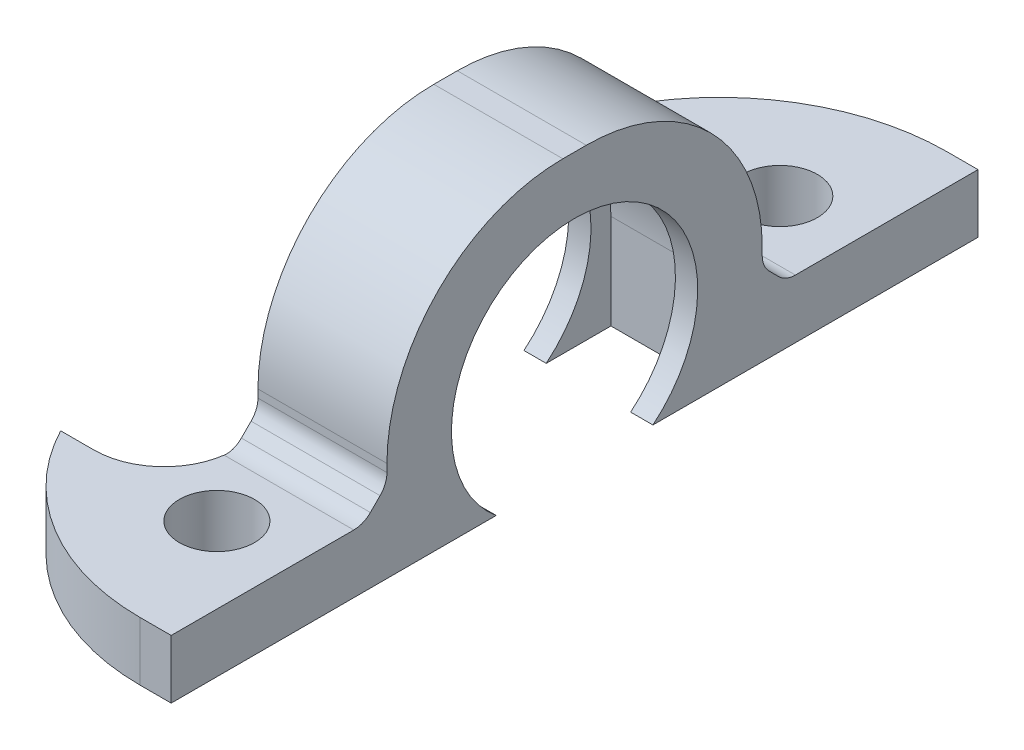
SolidWorks part; units mm, degrees
ref_plane "Front Plane" through (0, 0, 0) normal (0, 0, 1) x (1, 0, 0)
ref_plane "Top Plane" through (0, 0, 0) normal (0, 1, 0) x (1, 0, 0)
ref_plane "Right Plane" through (0, 0, 0) normal (1, 0, 0) x (0, 0, -1)
sketch "Sketch1" plane through (0, 0, 0) normal (0, 1, 0) x (1, 0, 0)
  line L1 (-7.5, -17.5) -> (7.5, -17.5)
  line L2 (-7.5, -17.5) -> (-7.5, 17.5)
  line L3 (-7.5, 17.5) -> (7.5, 17.5)
  line L4 (7.5, -17.5) -> (7.5, 17.5)
  line L5 (-7.5, -17.5) -> (7.5, 17.5) construction
  line L6 (-7.5, 17.5) -> (7.5, -17.5) construction
  point P0 (0, 0)
extrude "Boss-Extrude1" add sketch "Sketch1" along normal blind 2.5
sketch "Sketch2" plane through (0, 0, 0) normal (0, -1, 0) x (-1, 0, 0)
  point P0 (0, 0)
sketch "Sketch3" plane through (0, 0, 0) normal (0, -1, 0) x (1, 0, 0)
  line L0 (2.75, 17.5) -> (2.75, -17.5)
  line L1 (-7.5, 17.5) -> (7.5, 17.5) construction
  line L2 (2.75, 3.4004) -> (2.75, 17.5) construction
  line L3 (7.5, -17.5) -> (-7.5, -17.5) construction
  line L4 (2.75, -17.5) -> (2.75, -19.5) construction
  line M2 (7.5, -17.5) -> (7.5, 17.5)
  line M3 (7.5, 17.5) -> (-7.5, 17.5)
  line M5 (-7.5, -17.5) -> (7.5, -17.5)
extrude "Cut-Extrude2" cut sketch "Sketch3" against normal through all and the other way through all contours L0 M3 M5 M2 region at (5.125, 0, 0)
sketch "Sketch5" plane through (0, 2.5, 0) normal (0, 1, 0) x (1, 0, 0)
  line L0 (2.75, 0) -> (1.75, 0)
  line L1 (2.75, -17.5) -> (2.75, 17.5) construction
  line L2 (1.75, 0) -> (-1.75, 0)
  line L3 (-1.75, 0) -> (-2.75, 0)
  line L4 (-2.75, 0) -> (-8, 0)
  line L6 (-5.75, -12) -> (-10.25, -12)
  line L7 (-2.75, -9) -> (-2.75, 9)
  line L8 (-5.75, 12) -> (-10.25, 12)
  line L9 (-13.25, -9) -> (-13.25, 9)
  line L10 (-2.75, -12) -> (-13.25, 12) construction
  line L11 (-2.75, 12) -> (-13.25, -12) construction
  arc A0 (-10.25, -12) -> (-13.25, -9) centre (-10.25, -9) cw
  arc A1 (-5.75, -12) -> (-2.75, -9) centre (-5.75, -9) ccw
  arc A2 (-2.75, 9) -> (-5.75, 12) centre (-5.75, 9) ccw
  arc A3 (-10.25, 12) -> (-13.25, 9) centre (-10.25, 9) ccw
  line M12 (-7.5, 17.5) -> (-7.5, -17.5)
  dimension "D7" = 3
  dimension "D1" = 1
  dimension "D2" = 3.5
  dimension "D3" = 1
  dimension "D4" = 5.25
  dimension "D5" = 24
  dimension "D6" = 10.5
extrude "Cut-Extrude3" cut sketch "Sketch5" against normal through all contours L8 A3 L9 A0 L6 M12 | L7 A2 L8 L4 M12 | L6 A1 L7 L4 M12 region at (-5.1848, 2.5, 5.8131) region at (-5.1848, 2.5, -5.8131) region at (-10.3115, 2.5, 0)
fillet "Fillet1" radius 10 2 edges at (-7.5, 1.25, 17.5) (-7.5, 1.25, -17.5)
sketch "Sketch6" plane through (0, 2.5, 0) normal (0, 1, 0) x (1, 0, 0)
  line L13 (2.75, 17.2) -> (1.4303, 17.2)
  line L14 (2.75, 17.2) -> (1.4303, 17.2)
  line L16 (1.4303, -17.2) -> (2.75, -17.2)
  line L17 (1.4303, -17.2) -> (2.75, -17.2)
  arc A18 (1.4303, 17.2) -> (-7.2321, 11.865) centre (1.4303, 7.5) ccw
  arc A19 (1.4303, 17.2) -> (-7.2321, 11.865) centre (1.4303, 7.5) ccw
  arc A22 (-7.2321, -11.865) -> (1.4303, -17.2) centre (1.4303, -7.5) ccw
  arc A23 (-7.2321, -11.865) -> (1.4303, -17.2) centre (1.4303, -7.5) ccw
  line M11 (-5.75, -12) -> (-7.5, -12)
  arc M12 (-7.5, -12) -> (1.4303, -17.5) centre (1.4303, -7.5) ccw
  line M13 (1.4303, -17.5) -> (2.75, -17.5)
  line M14 (2.75, -17.5) -> (2.75, 17.5)
  line M15 (2.75, 17.5) -> (1.4303, 17.5)
  arc M16 (1.4303, 17.5) -> (-7.5, 12) centre (1.4303, 7.5) ccw
  line M17 (-7.5, 12) -> (-5.75, 12)
  dimension "D1" = 0.3
  dimension "D2" = 0.3
extrude "Cut-Extrude5" cut sketch "Sketch6" against normal through all contours A19 L14 M14 M15 M16 M17 | A23 L17 M11 M12 M13 M14 region at (2.6337, 2.5, 17.35) region at (2.0901, 2.5, -17.3163)
sketch "Sketch7" plane through (0, 2.5, 0) normal (0, 1, 0) x (1, 0, 0)
  line L0 (0, 0) -> (-0.5, 0)
  line L1 (-0.5, 0) -> (-0.5, 12)
  circle A0 centre (-0.5, 12) radius 1.6
  circle A1 centre (-0.5, -12) radius 1.6
  dimension "D1" = 3.2
  dimension "0.5" = 0.5
extrude "Cut-Extrude6" cut sketch "Sketch7" against normal through all contours A0 | A1 region at (0.5994, 2.5, -10.9006) region at (-0.5, 2.5, 12)
sketch "Sketch8" plane through (2.75, 0, 0) normal (1, 0, 0) x (0, 0, -1)
  line L0 (0, 2.5) -> (0, 4.05)
  line L1 (-17.2, 2.5) -> (17.2, 2.5) construction
  line L2 (8, 2.5) -> (-8, 2.5)
  line L3 (-8, 2.5) -> (-8, 4.5)
  line L4 (8, 2.5) -> (8, 4.5)
  line L5 (0.5, 12) -> (-0.5, 12)
  arc A0 (8, 4.5) -> (0.5, 12) centre (0.5, 4.5) ccw
  arc A1 (-8, 4.5) -> (-0.5, 12) centre (-0.5, 4.5) cw
  circle A2 centre (0, 4.05) radius 5.25
  circle A3 centre (0, 4.05) radius 6.05
  point P8 (0, 2.5)
  dimension "D2" = 7.5
  dimension "D1" = 16
sketch "Sketch9" plane through (2.75, 0, 0) normal (1, 0, 0) x (0, 0, -1)
  line L0 (0, 2.5) -> (-8, 2.5)
  line L1 (-8, 2.5) -> (-8, 4.25)
  line L2 (0, 2.5) -> (8, 2.5)
  line L3 (8, 2.5) -> (8, 4.25)
  line L4 (0.5, 11.75) -> (-0.5, 11.75)
  line L5 (0, 2.5) -> (0, 4.05)
  arc A0 (8, 4.25) -> (0.5, 11.75) centre (0.5, 4.25) ccw
  arc A1 (-8, 4.25) -> (-0.5, 11.75) centre (-0.5, 4.25) cw
  circle A4 centre (0, 4.05) radius 5.25
  line M9 (17.2, 2.5) -> (-17.2, 2.5)
  dimension "D1" = 7.5
  dimension "D2" = 1.75
  dimension "D3" = 10.5
extrude "Boss-Extrude2" add sketch "Sketch9" against normal up to surface (5.5 mm away) contours L3 A0 L4 A1 L1 L0 M9 region at (2.75, 2.6848, 6.508) up to face at (-2.75, 1.25, 0)
sketch "Sketch10" plane through (2.75, 0, 0) normal (1, 0, 0) x (0, 0, -1)
  line L0 (-6.1, 4.05) -> (-6.1, 0)
  line L1 (-17.2, 0) -> (17.2, 0) construction
  line L2 (6.1, 4.05) -> (6.1, 0)
  circle A0 centre (0, 4.05) radius 5.25
  circle A1 centre (0, 4.05) radius 6.1
  line M13 (-17.2, 0) -> (17.2, 0)
  dimension "D1" = 10.5
  dimension "D2" = 12.2
extrude "Cut-Extrude7" cut sketch "Sketch10" against normal blind 3.6 from offset 0.95 contours A1 A0 M13 | A1 L0 M13 | A1 L2 M13 region at (2.75, 0.9852, 5.6505) region at (2.75, 9.9913, 0) region at (2.75, 0.9852, -5.6505) offset against normal yes
sketch "Sketch11" plane through (2.75, 0, 0) normal (1, 0, 0) x (0, 0, -1)
  circle A0 centre (0, 4.05) radius 5.25
  dimension "D1" = 10.5
extrude "Cut-Extrude8" cut sketch "Sketch11" against normal through all
chamfer "Chamfer1" distance 1 angle 45 2 edges at (0, 2.5, 8) (0, 2.5, -8)
fillet "Fillet2" radius 1 4 edges at (0, 2.5, -9) (0, 3.5, -8) (0, 3.5, 8) (0, 2.5, 9)
